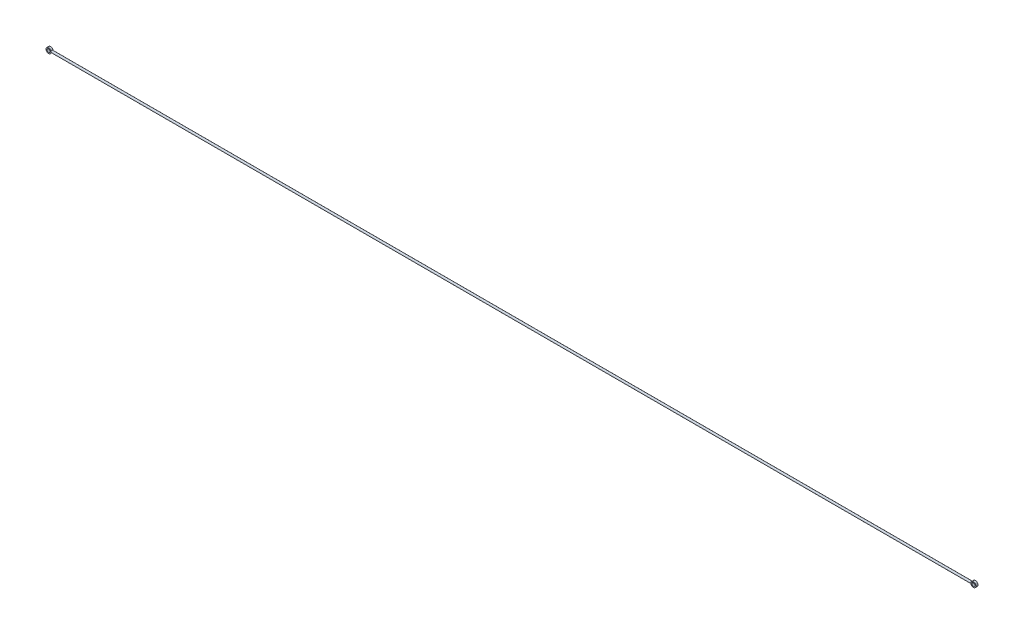
SolidWorks part; units mm, degrees
ref_plane "Alzado" through (0, 0, 0) normal (0, 0, 1) x (1, 0, 0)
ref_plane "Planta" through (0, 0, 0) normal (0, 1, 0) x (1, 0, 0)
ref_plane "Vista lateral" through (0, 0, 0) normal (1, 0, 0) x (0, 0, -1)
sketch "Croquis1" plane through (0, 0, 0) normal (0, 0, 1) x (1, 0, 0)
  line L0 (0, 0) -> (-450, 0)
  dimension "D1" = 450
sketch "Croquis2" plane through (0, 0, 0) normal (1, 0, 0) x (0, 0, -1)
  circle A0 centre (0, 0) radius 0.5
  dimension "D1" = 1
sweep "Barrer1" add profiles "Croquis2" path "Croquis1"
sketch "Croquis3" plane through (0, 0, 0) normal (0, 0, 1) x (1, 0, 0)
  circle A0 centre (1, 0) radius 1.25
  circle A1 centre (1, 0) radius 0.75
  circle A2 centre (-451, 0) radius 1.25
  circle A3 centre (-451, 0) radius 0.75
  dimension "D1" = 2.5
  dimension "D2" = 1.5
  dimension "D4" = 2.5
  dimension "D5" = 1.5
  dimension "D3" = 1
  dimension "D6" = 1
extrude "Saliente-Extruir1" add sketch "Croquis3" along normal blind 0.5 and the other way blind 0.5
